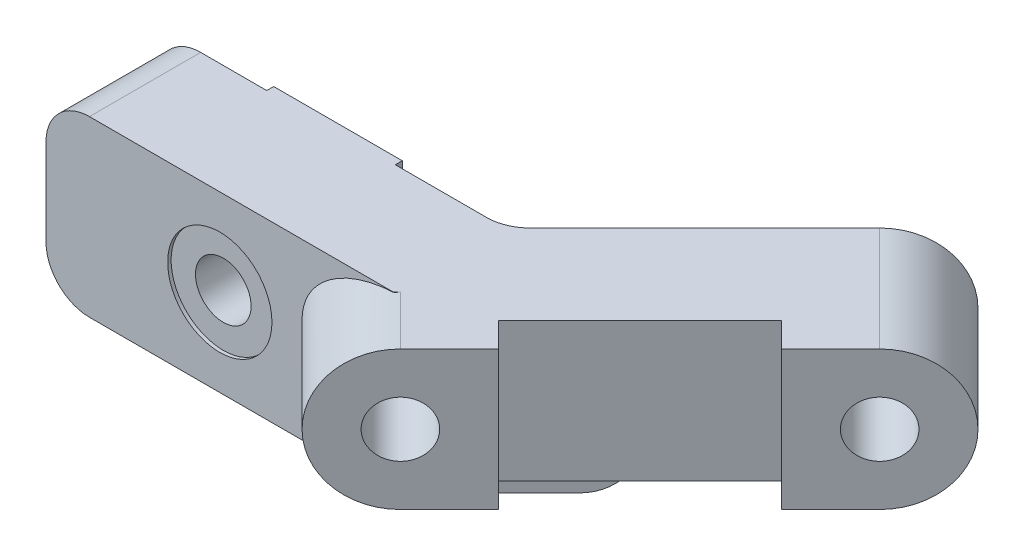
SolidWorks part; units mm, degrees
ref_plane "Спереди" through (0, 0, 0) normal (0, 0, 1) x (1, 0, 0)
ref_plane "Сверху" through (0, 0, 0) normal (0, 1, 0) x (1, 0, 0)
ref_plane "Справа" through (0, 0, 0) normal (1, 0, 0) x (0, 0, -1)
sketch "Эскиз1" plane through (0, 0, 0) normal (0, 0, 1) x (1, 0, 0)
  line L1 (0, 0) -> (20, 0)
  line L2 (0, 0) -> (0, -10)
  line L3 (0, -10) -> (20, -10)
  line L4 (20, 0) -> (20, -10)
  dimension "D1" = 10
  dimension "D2" = 20
extrude "Бобышка-Вытянуть1" add sketch "Эскиз1" along normal blind 6.4
sketch "Эскиз12" plane through (0, 0, 0) normal (0, 1, 0) x (1, 0, 0)
  line L0 (20, 0) -> (23.8891, 3.8891)
  line L1 (23.8891, 3.8891) -> (27.0891, 0.6891)
  line L2 (27.0891, 0.6891) -> (20, -6.4)
  line L3 (20, -6.4) -> (0, -6.4) construction
  line L4 (20, 0) -> (0, 0) construction
  line L5 (20, 0) -> (20, -6.4)
  dimension "D1" = 45
  dimension "D2" = 5.5
extrude "Бобышка-Вытянуть6" add sketch "Эскиз12" against normal up to surface (10 mm away) up to face at (10, -10, 3.2)
sketch "Эскиз4" plane through (4.7188, 0, 21.6812) normal (-0.7071, 0, -0.7071) x (-0.7071, 0, 0.7071)
  line L0 (-21.8864, -8) -> (-41.3864, -8)
  line L1 (-21.8864, 0) -> (-41.3864, 0)
  line L4 (-21.6109, 0) -> (-7.4688, 0) construction
  line L5 (-31.6364, -10) -> (-31.6364, 0) construction
  arc A0 (-21.8864, -8) -> (-21.8864, 0) centre (-21.8864, -4) ccw
  arc A1 (-41.3864, 0) -> (-41.3864, -8) centre (-41.3864, -4) ccw
  point P9 (-31.6364, -8)
  dimension "D1" = 8
  dimension "D2" = 8
  dimension "D3" = 19.5
  dimension "D5" = 8
extrude "Бобышка-Вытянуть3" add sketch "Эскиз4" against normal blind 2 and the other way up to surface (4.5255 mm away) other way up to face at (21.9445, -5, -1.9445)
sketch "Эскиз14" plane through (14.6142, 0, 14.6142) normal (0.7071, 0, 0.7071) x (0.7071, 0, -0.7071)
  line L8 (29.3921, -8) -> (25.3921, -8)
  line L9 (29.3921, -8) -> (9.8921, -8) construction
  line L10 (25.3921, -8) -> (25.3921, 0)
  line L11 (9.8921, 0) -> (29.3921, 0) construction
  line L12 (25.3921, 0) -> (29.3921, 0)
  line L13 (9.8921, -8) -> (13.8921, -8)
  line L14 (13.8921, -8) -> (13.8921, 0)
  line L15 (13.8921, 0) -> (9.8921, 0)
  arc A4 (9.8921, 0) -> (9.8921, -8) centre (9.8921, -4) ccw construction
  arc A5 (29.3921, -8) -> (29.3921, 0) centre (29.3921, -4) ccw construction
  arc A6 (9.8921, 0) -> (9.8921, -8) centre (9.8921, -4) ccw
  arc A7 (29.3921, -8) -> (29.3921, 0) centre (29.3921, -4) ccw
  dimension "D1" = 4
  dimension "D2" = 4
extrude "Бобышка-Вытянуть7" add sketch "Эскиз14" along normal blind 2
sketch "Эскиз11" plane through (0, 0, 0) normal (0, 0, -1) x (-1, 0, 0)
  line L1 (-6.3, -10) -> (-13.7, -10)
  line L2 (-6.3, -10) -> (-6.3, 0)
  line L3 (-6.3, 0) -> (-13.7, 0)
  line L4 (-13.7, -10) -> (-13.7, 0)
  line L6 (0, -10) -> (-20, -10) construction
  line L7 (-20, 0) -> (0, 0) construction
  line L8 (0, 0) -> (0, -10) construction
  point P8 (-10, 0)
  dimension "D1" = 10
  dimension "D2" = 7.4
  dimension "D3" = 10
extrude "Бобышка-Вытянуть5" add sketch "Эскиз11" along normal blind 0.4
sketch "Эскиз6" plane through (16.0284, 0, 16.0284) normal (0.7071, 0, 0.7071) x (0.7071, 0, -0.7071)
  circle A0 centre (9.8921, -4) radius 1.6
  circle A1 centre (29.3921, -4) radius 1.6
  dimension "D1" = 3.2
  dimension "D2" = 3.2
extrude "Вырез-Вытянуть2" cut sketch "Эскиз6" against normal through all
sketch "Эскиз7" plane through (34.1421, 0, -14.1421) normal (0.7071, 0, 0.7071) x (0.7071, 0, -0.7071)
  line L1 (-1.5168, -4) -> (-3.1334, -1.2)
  line L2 (-3.1334, -1.2) -> (-6.3666, -1.2)
  line L3 (-6.3666, -1.2) -> (-7.9832, -4)
  line L4 (-7.9832, -4) -> (-6.3666, -6.8)
  line L5 (-6.3666, -6.8) -> (-3.1334, -6.8)
  line L6 (-3.1334, -6.8) -> (-1.5168, -4)
  line L7 (-27.4832, -4) -> (-25.8666, -6.8)
  line L8 (-25.8666, -6.8) -> (-22.6334, -6.8)
  line L9 (-22.6334, -6.8) -> (-21.0168, -4)
  line L10 (-21.0168, -4) -> (-22.6334, -1.2)
  line L11 (-22.6334, -1.2) -> (-25.8666, -1.2)
  line L12 (-25.8666, -1.2) -> (-27.4832, -4)
  circle A0 centre (-4.75, -4) radius 2.8 construction
  circle A1 centre (-24.25, -4) radius 2.8 construction
  dimension "D1" = 5.6
  dimension "D2" = 5.6
extrude "Вырез-Вытянуть3" cut sketch "Эскиз7" along normal blind 2.6 and the other way through all
hole_wizard "Цековка для  болта с шестигранной головкой M51" positions "Трехмерный эскиз1" profile "Эскиз9" counterbore size "M5" standard "ISO"
sketch3d "Трехмерный эскиз1"
  line L0 (0, 0, 6.4) -> (0, -10, 6.4) construction
  point P0 (10, -5, 6.4)
  point P7 (0, -5, 6.4)
  dimension "D1" = 10
sketch "Эскиз9" plane through (10, -5, 6.4) normal (1, 0, 0) x (0, -1, 0)
  line L0 (0, 0) -> (0, 22.9614)
  line L1 (0, 22.9614) -> (1.6, 22)
  line L2 (1.6, 22) -> (1.6, 0.2)
  line L3 (1.6, 0.2) -> (3, 0.2)
  line L4 (3, 0.2) -> (3, 0)
  line L5 (3, 0) -> (0, 0)
  line L10 (0, 22.9614) -> (-1.6, 22) construction
  line L11 (0, -6.35) -> (0, 107.95) construction
  dimension "Диаметр отверстия" = 3.2
  dimension "Глубина отверстия" = 22
  dimension "Диаметр цековки" = 6
  dimension "Глубина цековки" = 0.2
  dimension "Угол заточки сверла" = 118
fillet "Скругление1" radius 2.5 5 edges at (20, -5, 0) (0, 0, 3.2) (0, -10, 3.2) (25.4891, -10, -2.2891) (20, -8.9953, 6.4)
